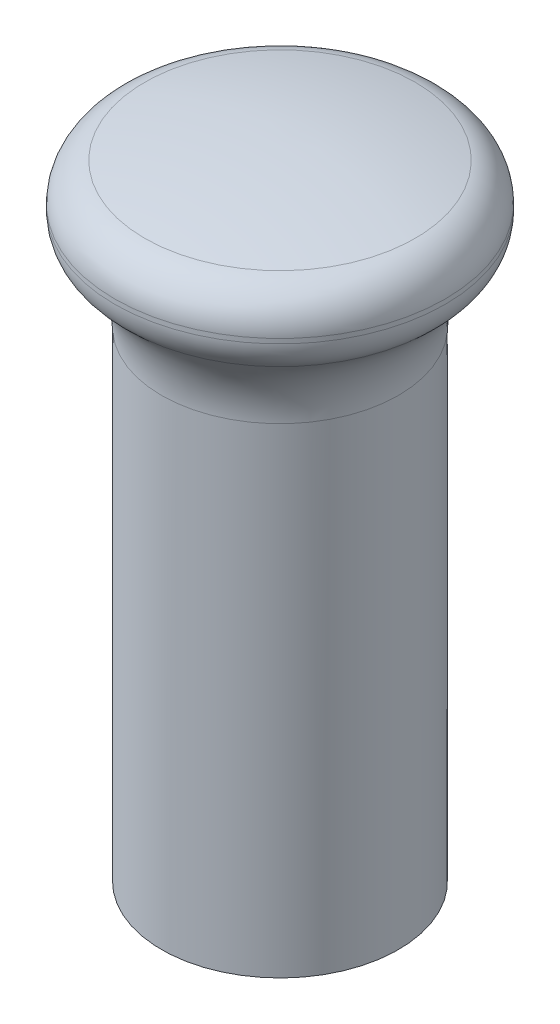
SolidWorks part; units mm, degrees
material "6061-T6 (SS)"
ref_plane "Front Plane" through (0, 0, 0) normal (0, 0, 1) x (1, 0, 0)
ref_plane "Top Plane" through (0, 0, 0) normal (0, 1, 0) x (1, 0, 0)
ref_plane "Right Plane" through (0, 0, 0) normal (1, 0, 0) x (0, 0, -1)
sketch "Sketch1" plane through (0, 0, 0) normal (1, 0, 0) x (0, 0, -1)
  line L0 (0, 25.4) -> (0, 46.4566) construction
  line L1 (3.6957, 25.4) -> (-3.6957, 25.4) construction
  line L2 (4.8966, 14.7066) -> (-5.3865, 14.7066) construction
  line L3 (0, 46.4566) -> (5.4356, 46.4566) construction
  line L4 (5.4356, 46.4566) -> (5.4356, 43.9166) construction
  line L5 (5.4356, 43.9166) -> (3.899, 43.9166)
  line L6 (3.899, 43.9166) -> (3.899, 25.4)
  line L7 (3.899, 25.4) -> (0, 25.4)
  line L8 (0, 25.4) -> (0, 46.4566)
  line L9 (5.4356, 45.6946) -> (5.4356, 43.9166)
  arc A0 (5.4356, 45.6946) -> (0, 46.4566) centre (0, 26.6886) ccw
  dimension "D1" = 31.75
  dimension "D2" = 7.798
  dimension "D3" = 5.4356
  dimension "D4" = 2.54
  dimension "D5" = 0.762
revolve "Revolve1" add sketch "Sketch1" angle 360 about L0
fillet "Fillet1" radius 3.175 1 edges at (0, 43.9166, -3.899)
fillet "Fillet2" radius 1.27 2 edges at (0, 45.6946, -5.4356) (0, 43.9166, -5.4356)
